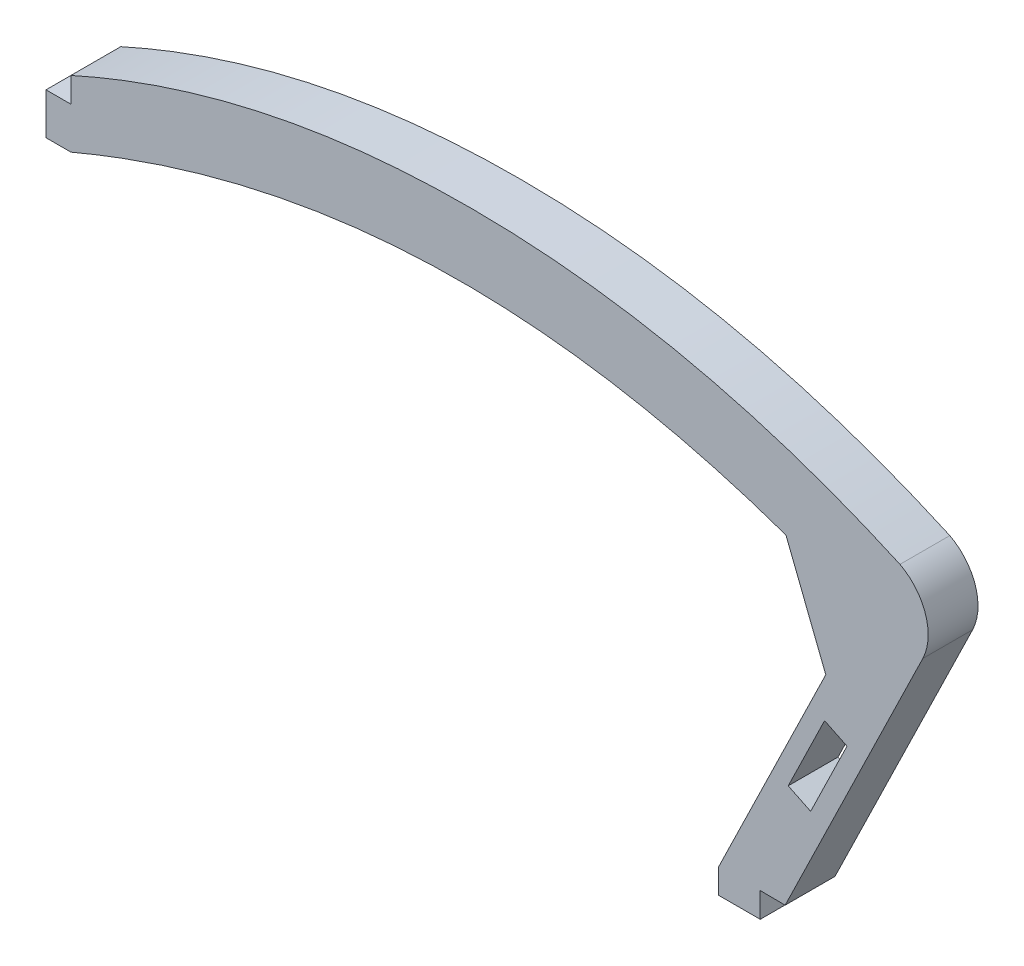
SolidWorks part; units mm, degrees
ref_plane "Front" through (0, 0, 0) normal (0, 0, 1) x (1, 0, 0)
ref_plane "Top" through (0, 0, 0) normal (0, 1, 0) x (1, 0, 0)
ref_plane "Right" through (0, 0, 0) normal (1, 0, 0) x (0, 0, -1)
sketch "Sketch1" plane through (0, 0, 0) normal (0, 0, 1) x (1, 0, 0)
  line L0 (5, 0) -> (7.9999, -0.0223)
  line L1 (-81, 40.5) -> (-78, 40.5)
  line L2 (0, 0) -> (0, -3)
  line L3 (0, -3) -> (5, -3)
  line L4 (5, 0) -> (5, -3)
  line L5 (7.9999, -0.0223) -> (24.5748, 33.9889)
  line L6 (0, 0) -> (17.0927, 35.0737)
  line L7 (-81, 40.5) -> (-81, 35.5)
  line L8 (-81, 35.5) -> (-78, 35.5)
  line L9 (-78, 40.5) -> (-78, 43.5)
  arc A1 (24.5748, 33.9889) -> (21.0498, 42.7793) centre (18.8316, 36.7878) ccw
  spline S0 degree 2 poles (17.0927, 35.0737) (-30.3833, 55.7116) (-78, 35.5) knots 0 0 0 1 1 1
  spline S1 degree 3 poles (21.8265, 42.4313) (4.3035, 50.3434) (-29.0264, 57.0183) (-62.2418, 50.6205) (-78, 43.5) knots 0.018385 0.018385 0.018385 0.018385 0.528856 0.991085 0.991085 0.991085 0.991085
  point P12 (-30.6479, 45)
  point P13 (25, 40)
  point P14 (-30.6479, 45)
  point P20 (0, 0)
  dimension "D7" = 3
  dimension "D1" = 3
  dimension "D2" = 5
  dimension "D3" = 40
  dimension "D4" = 20
  dimension "D5" = 106
  dimension "D6" = 5
  dimension "D8" = 10
  dimension "D9" = 3
  dimension "D10" = 5
  dimension "D11" = 35.5
  dimension "D12" = 360
  dimension "D13" = 7.2012
  dimension "D14" = 3
extrude "Boss-Extrude1" add sketch "Sketch1" along normal blind 6 contours L7 L8 L6 region at (3.7957, -1.5, 0)
chamfer "Chamfer1" distance 10 angle 45 1 edges at (17.0927, 35.0737, 3) first distance on face at (-6.6805, 35.1802, 3)
sketch "Sketch4" plane through (0, 0, 6) normal (0, 0, 1) x (1, 0, 0)
  line L0 (8.3691, 12.6078) -> (12.75, 21.5972)
  line L1 (12.75, 21.5972) -> (15.4468, 20.2829)
  line L2 (15.4468, 20.2829) -> (11.0659, 11.2936)
  line L3 (11.0659, 11.2936) -> (8.3691, 12.6078)
  line L4 (0, 0) -> (12.8902, 26.4504) construction
  dimension "D1" = 3
  dimension "D2" = 2
  dimension "D3" = 10
  dimension "D4" = 15
extrude "Cut-Extrude1" cut sketch "Sketch4" against normal blind 6
